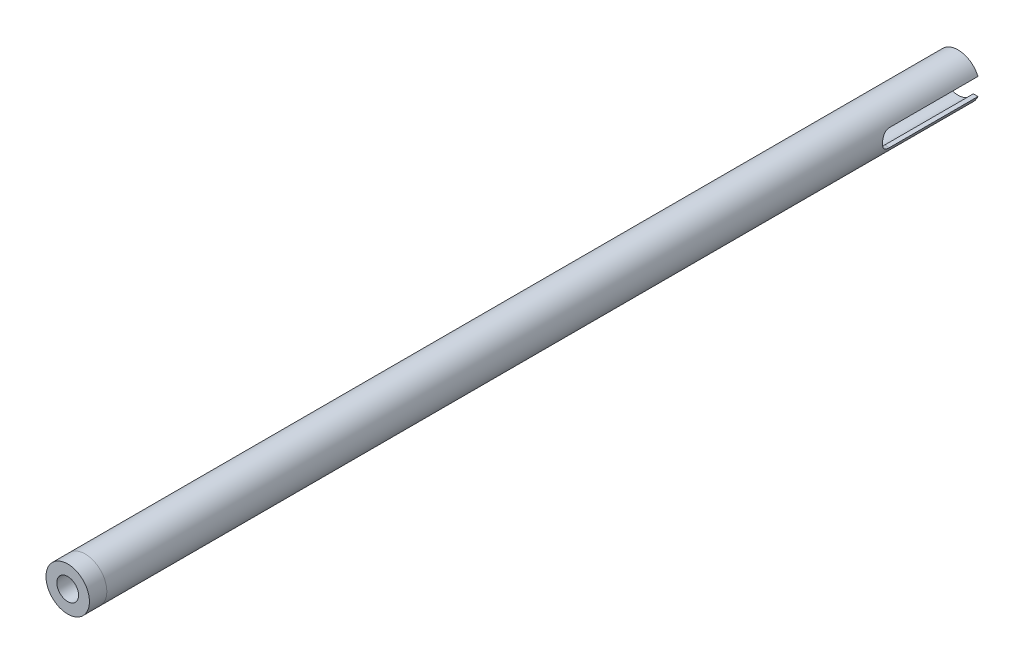
SolidWorks part; units mm, degrees
ref_plane "Front Plane" through (0, 0, 0) normal (0, 0, 1) x (1, 0, 0)
ref_plane "Top Plane" through (0, 0, 0) normal (0, 1, 0) x (1, 0, 0)
ref_plane "Right Plane" through (0, 0, 0) normal (1, 0, 0) x (0, 0, -1)
sketch "Axis" plane through (0, 0, 0) normal (0, 1, 0) x (1, 0, 0)
  line L0 (0, 0) -> (0, 325.114) construction
  line L1 (0, 0) -> (0, -34.925) construction
  line L2 (0, 325.114) -> (-7.9375, 325.114) construction
  line L3 (0, 354.4828) -> (-10.3188, 316.3034) construction
  dimension "D1" = 34.925
  dimension "D2" = 7.9375
sketch "Sketch1" plane through (0, 0, 0) normal (0, 0, 1) x (1, 0, 0)
  line L0 (-7.9375, 0) -> (7.9375, 0) construction
  line L1 (-7.2748, 3.175) -> (7.2748, 3.175)
  line L2 (-7.2748, -3.175) -> (7.2748, -3.175)
  circle A0 centre (0, 0) radius 7.9375
  circle A1 centre (0, 0) radius 6.4135
  circle A2 centre (0, 0) radius 3.9688
  dimension "D1" = 15.875
  dimension "D3" = 7.9375
  dimension "D2" = 1.524
  dimension "D4" = 6.35
extrude "Threaded insert 1-1" add sketch "Sketch1" against normal blind 6.35 contours A2 L1 A1 | A1 L1 A0 | A2 L0 A1 L1 | A1 L0 A0 L1 | L0 A1 L2 A0 | L0 A2 L2 A1 | A2 L2 A1 | A1 L2 A0 | L0 A1 L2 A2 | L0 A0 L2 A1 | A0 L0 A1 L1 | A1 L0 A2 L1 region at (4.7887, 1.6543, 0) region at (4.7887, -1.6543, 0) region at (6.9234, 1.6163, 0) region at (6.9234, -1.6163, 0) region at (-4.7887, -1.6543, 0) region at (-4.7887, 1.6543, 0) region at (0, 4.6159, 0) region at (0, -4.6159, 0) region at (0, 6.5666, 0) region at (6.4237, -3.3281, 0) region at (-6.9234, -1.6163, 0) region at (-6.9234, 1.6163, 0)
extrude "Threaded insert 1-2" add sketch "Sketch1<3>" against normal blind 9.525 from surface contours A2 L1 A1 | A2 L0 A1 L1 | L0 A2 L2 A1 | A2 L2 A1 | L0 A1 L2 A2 | A1 L0 A2 L1 region at (4.7887, 1.6543, 0) region at (4.7887, -1.6543, 0) region at (-4.7887, -1.6543, 0) region at (-4.7887, 1.6543, 0) region at (0, 4.6159, 0) region at (0, -4.6159, 0) starting at face at (7.9375, 0, -6.35)
sketch "Sketch1<3>" plane through (0, 0, 0) normal (0, 0, 1) x (1, 0, 0) same geometry as "Sketch1"
extrude "A-arm tube" add sketch "Sketch1<4>" against normal up to vertex (325.114 mm away) from surface separate body contours A1 L1 A0 | A1 L0 A0 L1 | L0 A1 L2 A0 | A1 L2 A0 | L0 A0 L2 A1 | A0 L0 A1 L1 region at (6.9234, 1.6163, 0) region at (6.9234, -1.6163, 0) region at (0, 6.5666, 0) region at (6.4237, -3.3281, 0) region at (-6.9234, -1.6163, 0) region at (-6.9234, 1.6163, 0) up to point (0, 0, -325.114) starting at face at (6.4135, 0, -6.35)
sketch "Sketch1<4>" plane through (0, 0, 0) normal (0, 0, 1) x (1, 0, 0) same geometry as "Sketch1"
extrude "Apex slot" cut sketch "Sketch1<5>" along normal blind 35.56 from surface contours A0 L0 A1 L1 | L0 A0 L2 A1 | A1 L0 A0 L1 | L0 A1 L2 A0 region at (6.9234, 1.6163, 0) region at (6.9234, -1.6163, 0) region at (-6.9234, -1.6163, 0) region at (-6.9234, 1.6163, 0) starting at face at (6.4135, 0, -325.114)
sketch "Sketch1<5>" plane through (0, 0, 0) normal (0, 0, 1) x (1, 0, 0) same geometry as "Sketch1"
fillet "Fillet1" radius 3.175 4 edges at (-6.4237, 3.175, -289.554) (-6.4237, -3.175, -289.554) (6.4237, -3.175, -289.554) (6.4237, 3.175, -289.554)
equation "\"tube diameter\"= 5 / 8"
equation "\"tube thickness\"= .06"
equation "\"apex thickness\"= .25"
equation "\"tube slot\"= 1.4"
equation "\"D1@Sketch1\"=\"tube diameter\""
equation "\"D2@Sketch1\"=\"tube thickness\""
equation "\"threaded insert hole\"= .3125"
equation "\"D3@Sketch1\"=\"threaded insert hole\""
equation "\"D4@Sketch1\"=\"apex thickness\""
equation "\"D1@Apex slot\" = \"tube slot\""
equation "\"D1@Fillet1\"=\"apex thickness\"/2"
equation "\"D2@Axis\"=\"tube diameter\"/2"
